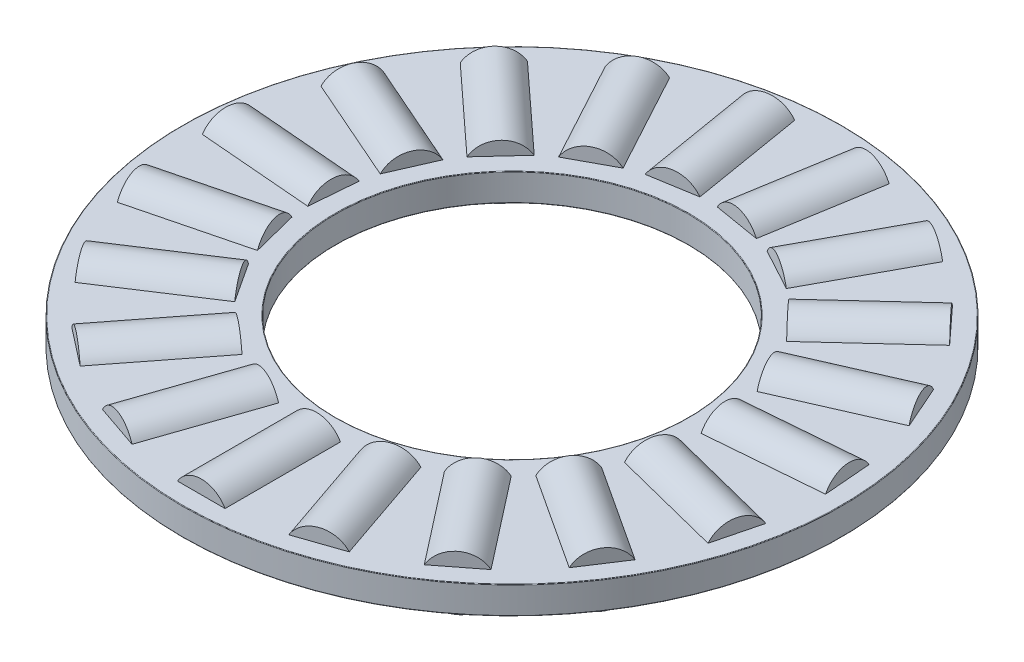
SolidWorks part; units mm, degrees
ref_plane "Front Plane" through (0, 0, 0) normal (0, 0, 1) x (1, 0, 0)
ref_plane "Top Plane" through (0, 0, 0) normal (0, 1, 0) x (1, 0, 0)
ref_plane "Right Plane" through (0, 0, 0) normal (1, 0, 0) x (0, 0, -1)
sketch "Sketch1" plane through (0, 0, 0) normal (1, 0, 0) x (0, 0, -1)
  line L0 (-11.9062, 0) -> (11.9062, 0) construction
  line L1 (0, -0.9922) -> (0, 0.9922) construction
  line L2 (-11.9063, 0.4961) -> (-6.3754, 0.4961)
  line L3 (-11.9063, 0.4961) -> (-11.9063, -0.4961)
  line L4 (-11.9063, -0.4961) -> (-6.3754, -0.4961)
  line L5 (-6.3754, 0.4961) -> (-6.3754, -0.4961)
  line L7 (-9.1408, 0.9922) -> (-9.1408, 0.4961) construction
  line L8 (-11.2244, 0.9922) -> (-7.0572, 0.9922) construction
  line L9 (-11.2244, 0.9922) -> (-11.2244, -0.9922) construction
  line L10 (-11.2244, -0.9922) -> (-7.0572, -0.9922) construction
  line L11 (-7.0572, 0.9922) -> (-7.0572, -0.9922) construction
  point P16 (-11.2244, 0)
  dimension "OD" = 23.8125
  dimension "Shaft Dia" = 12.7508
  dimension "Th" = 1.9844
  dimension "D2" = 0.9922
  dimension "D1" = 4.1672
  dimension "D3" = 5.5309
revolve "Revolve1" add sketch "Sketch1" angle 360 about L1
sketch "Sketch3" plane through (0, 0, 0) normal (1, 0, 0) x (0, 0, -1)
  line L0 (-11.2244, 0.9922) -> (-11.2244, -0.9922) construction
  line L1 (-11.2244, 0) -> (-7.0572, 0)
  line L2 (-11.2244, 0) -> (-11.2244, 0.9922)
  line L3 (-11.2244, 0.9922) -> (-7.0572, 0.9922)
  line L4 (-7.0572, 0) -> (-7.0572, 0.9922)
revolve "Cut-Revolve1" cut sketch "Sketch3" angle 360 about L1
sketch "Sketch2" plane through (0, 0, 0) normal (1, 0, 0) x (0, 0, -1)
  line L1 (-11.2244, 0) -> (-7.0572, 0)
  line L2 (-11.2244, 0) -> (-11.2244, 0.9922)
  line L3 (-11.2244, 0.9922) -> (-7.0572, 0.9922)
  line L4 (-7.0572, 0) -> (-7.0572, 0.9922)
revolve "Revolve2" add sketch "Sketch2" angle 360 about L1
ref_axis "Axis1" through (0, 0.9922, 0) along (0, -1, 0)
pattern_circular "CirPattern1" count 19 every 18.947 about axis through (0, 0.9922, 0) along (0, -1, 0) of bodies 187 411
pattern_circular "CirPattern2" count 19 every 18.947 about axis through (0, 0.9922, 0) along (0, -1, 0) of "Cut-Revolve1"
sketch "Sketch4" plane through (0, 0, 0) normal (1, 0, 0) x (0, 0, -1)
  line L0 (-11.9063, 0.4961) -> (-11.9063, -0.4961) construction
  line L1 (-11.9062, 9.1091) -> (-6.35, 9.1091)
  line L2 (-11.9062, 9.1091) -> (-11.9062, 9.9219)
  line L3 (-11.9062, 9.9219) -> (-6.35, 9.9219)
  line L4 (-6.35, 9.1091) -> (-6.35, 9.9219)
  line L5 (-11.9062, -9.9219) -> (-6.3754, -9.9219)
  line L6 (-11.9062, -9.9219) -> (-11.9062, -9.1091)
  line L7 (-11.9062, -9.1091) -> (-6.3754, -9.1091)
  line L8 (-6.3754, -9.9219) -> (-6.3754, -9.1091)
  line L10 (-6.3754, 0.4961) -> (-6.3754, -0.4961) construction
  line L11 (0, 0) -> (-11.9062, 0) construction
  line L12 (-11.9062, 0) -> (11.9062, 0) construction
  line L13 (0, -0.9922) -> (0, 0.9922) construction
  dimension "Ht" = 19.8438
  dimension "Washer Th" = 0.8128
  dimension "Washer ID" = 12.7
  dimension "Washer OD" = 23.8125
fillet "Fillet2" radius 0.0198 4 edges at (0, -0.4961, -6.3754) (0, 0.4961, -6.3754) (0, -0.4961, -11.9063) (0, 0.4961, -11.9063)
equation "\"D2@Sketch1\"= \"Th@Sketch1\" * .5"
equation "\"Rollers@CirPattern1\"= \"OD@Sketch1\" * 20"
equation "\"Angle@CirPattern1\" = 360/\"Rollers@CirPattern1\""
equation "\"D1@CirPattern2\" = \"Rollers@CirPattern1\""
equation "\"D2@CirPattern2\" = \"Angle@CirPattern1\""
equation "\"Ht@Sketch4\" = \"Th@Sketch1\"*10"
